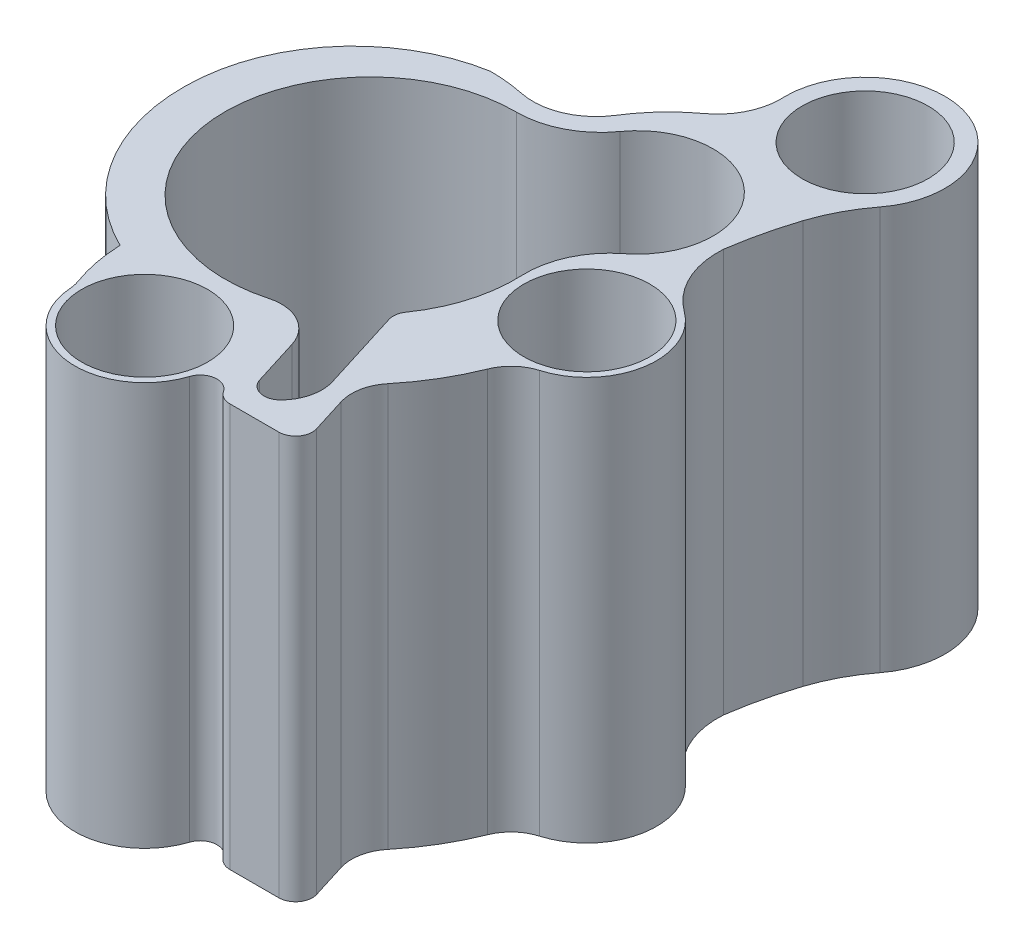
SolidWorks part; units mm, degrees
ref_plane "Front Plane" through (0, 0, 0) normal (0, 0, 1) x (1, 0, 0)
ref_plane "Top Plane" through (0, 0, 0) normal (0, 1, 0) x (1, 0, 0)
ref_plane "Right Plane" through (0, 0, 0) normal (1, 0, 0) x (0, 0, -1)
sketch "Sketch1" plane through (0, 0, 0) normal (0, 1, 0) x (1, 0, 0)
  line L0 (0, 17.0554) -> (0, -17.0554) construction
  line L1 (0, 0) -> (16.3625, 0) construction
  line L2 (5.7372, -9.3535) -> (8.3382, -17.6754)
  line L4 (11.8602, -12.8845) -> (13.7545, -18.9454)
  line L5 (13.7545, -18.9454) -> (7.4045, -18.9454)
  line L6 (6.6404, -16.5007) -> (7.4045, -18.9454)
  line L7 (8.3382, -17.6754) -> (12.027, -17.6754)
  line L8 (12.027, -17.6754) -> (8.6233, -6.7853)
  arc A0 (8.6233, -6.7853) -> (5.7372, -9.3535) centre (0, 0) ccw
  arc A1 (-6.188, 12.7228) -> (-6.188, -12.7228) centre (0, 0) ccw
  arc A2 (5.2705, 17.0554) -> (-5.2705, 17.0554) centre (0, 17.0554) ccw
  arc A4 (16.3625, -5.2705) -> (16.3625, 5.2705) centre (16.3625, 0) ccw
  circle A5 centre (0, 17.0554) radius 4.7625
  circle A6 centre (16.3625, 0) radius 4.7625
  arc A7 (5.2705, -17.0554) -> (-5.2705, -17.0554) centre (0, -17.0554) cw
  circle A8 centre (0, -17.0554) radius 4.7625
  arc A9 (5.2705, 17.0554) -> (16.3625, 5.2705) centre (-2.7565, -1.6119) cw
  arc A10 (16.3625, -5.2705) -> (11.8602, -12.8845) centre (-0.7121, -0.3122) cw
  arc A11 (6.6404, -16.5007) -> (5.2705, -17.0554) centre (-0.7121, -0.3122) cw
  arc A12 (-5.2705, -17.0554) -> (-6.188, -12.7228) centre (6.5049, -12.2983) cw
  arc A13 (-5.2705, 17.0554) -> (-6.188, 12.7228) centre (6.5049, 12.2983) ccw
  point P1 (0, 0)
  point P28 (17.145, 0)
  point P30 (15.7579, 0)
  point P31 (14.8475, 0)
  point P32 (0, 17.0554)
  point P33 (0, 0)
  dimension "D1" = 21.9456
  dimension "D2" = 3.175
  dimension "D4" = 9.525
  dimension "D3" = 9.525
  dimension "D5" = 0.508
  dimension "D6" = 0.508
  dimension "D7" = 20.32
  dimension "D8" = 17.78
  dimension "D13" = 12.7
  dimension "D14" = 6.188
  dimension "D9" = 6.35
  dimension "D10" = 6.35
  dimension "D11" = 6.35
  dimension "D12" = 6.0609
  dimension "D15" = 1.27
  dimension "D16" = 1.27
  dimension "D17" = 1.27
extrude "Boss-Extrude2" add sketch "Sketch1" along normal blind 30.48
fillet "Fillet1" radius 3.175 9 edges at (5.7372, 15.24, 9.3535) (11.8602, 15.24, 12.8845) (5.2705, 15.24, -17.0554) (-5.2705, 15.24, -17.0554) (-5.2705, 15.24, 17.0554) (5.2705, 15.24, 17.0554) (16.3625, 15.24, 5.2705) (16.3625, 15.24, -5.2705) (-6.188, 15.24, -12.7228)
fillet "Fillet3" radius 1.27 2 edges at (13.7545, 15.24, 18.9454) (7.4045, 15.24, 18.9454)
fillet "Fillet4" radius 3.175 1 edges at (12.027, 15.24, 17.6754)
fillet "Fillet5" radius 1.27 1 edges at (8.3382, 15.24, 17.6754)
fillet "Fillet6" radius 1.27 2 edges at (6.6404, 15.24, 16.5007) (8.6233, 15.24, 6.7853)
sketch "Sketch2" plane through (0, 30.48, 0) normal (0, 1, 0) x (1, 0, 0)
  circle A5 centre (9.8968, 10.2919) radius 5.715
  circle A6 centre (9.8968, 10.2919) radius 6.985
  circle A8 centre (0, 0) radius 10.9728
  arc M14 (17.7713, 5.0787) -> (15.7312, 6.8206) centre (18.6199, 8.1382) cw
  arc M15 (15.7312, 6.8206) -> (6.6953, 16.376) centre (-2.7565, -1.6119) ccw
  arc M16 (6.6953, 16.376) -> (5.0999, 18.3854) centre (8.1722, 19.1866) cw
  arc M24 (2.9092, -10.5801) -> (8.9879, -6.2944) centre (0, 0) cw
  dimension "D1" = 11.43
  dimension "D2" = 1.27
extrude "Boss-Extrude9" add sketch "Sketch2" against normal up to surface (30.48 mm away) contours A6 A5 M14 M16 M15 region at (13.2604, 30.48, -15.0944) up to face at (16.3625, 0, 4.7625)
extrude "Cut-Extrude6" cut sketch "Sketch2<12>" against normal blind 30.48 contours A5 M24 M15 region at (9.5924, 30.48, -10.0648)
sketch "Sketch2<12>" plane through (0, 30.48, 0) normal (0, 1, 0) x (1, 0, 0) same geometry as "Sketch2"
fillet "Fillet9" radius 6.35 4 edges at (6.5804, 15.24, -16.4395) (15.8349, 15.24, -6.6137) (9.9724, 15.24, -4.5774) (4.1837, 15.24, -10.1439)
sketch "Sketch3" plane through (0, 30.48, 0) normal (0, 1, 0) x (1, 0, 0)
  line L0 (-7.5055, 11.9928) -> (-2.2961, 12.883)
  line L1 (4.7625, 17.0554) -> (9.7342, 17.2751)
  arc A0 (-7.5055, 11.9928) -> (9.7342, 17.2751) centre (1.4545, 13.5239) cw
  circle A1 centre (0, 17.0554) radius 4.7625 construction
  arc A2 (-2.2961, 12.883) -> (4.7625, 17.0554) centre (0, 17.0554) ccw
extrude "Cut-Extrude7" cut sketch "Sketch3" against normal through all both and the other way through all
sketch "Sketch4" plane through (0, 30.48, 0) normal (0, 1, 0) x (1, 0, 0)
  arc A0 (19.1055, 17.5548) -> (9.2013, 21.7865) centre (15.2215, 22.1706) ccw
  circle A1 centre (15.2215, 22.1706) radius 4.7625
  arc A4 (16.8659, 9.822) -> (9.7342, 17.2751) centre (9.8968, 10.2919) ccw construction
  arc A5 (4.7625, 17.0554) -> (9.189, 22.1706) centre (4.4182, 21.8263) ccw
  arc A6 (19.1055, 17.5548) -> (16.8659, 9.822) centre (45.2516, 5.7916) ccw
  arc M14 (16.8659, 9.822) -> (9.7342, 17.2751) centre (9.8968, 10.2919) ccw
  line M15 (9.7342, 17.2751) -> (4.7625, 17.0554)
  dimension "D1" = 1.27
  dimension "D2" = 9.525
extrude "Boss-Extrude11" add sketch "Sketch4" against normal up to surface (30.48 mm away) contours A6 A0 A5 A1 M15 M14 region at (17.4758, 30.48, -13.8361) up to face at (7.0011, 0, 6.0805)
fillet "Fillet10" radius 12.7 3 edges at (19.1055, 15.24, -17.5548) (-7.5055, 15.24, -11.9928) (4.7625, 15.24, -17.0554)
fillet "Fillet11" radius 12.7 1 edges at (-2.2961, 15.24, -12.883)
sketch "Sketch5" plane through (0, 30.48, 0) normal (0, 1, 0) x (1, 0, 0)
  line B0 (8.816, -7.4018) -> (10.7572, -13.6127)
  line B1 (6.7814, -12.6943) -> (7.8936, -16.253)
  line B2 (8.3382, -18.9454) -> (12.027, -18.9454)
  line B3 (13.2392, -17.2965) -> (12.4021, -14.6183)
  circle B4 centre (15.2215, 22.1706) radius 4.7625
  circle B5 centre (16.3625, 0) radius 4.7625
  circle B6 centre (0, -17.0554) radius 4.7625
  arc B7 (0.0582, 10.9726) -> (2.9092, -10.5801) centre (0, 0) ccw
  arc B8 (13.4063, 5.7814) -> (5.2524, 13.6222) centre (9.8968, 10.2919) ccw
  arc B9 (0.0582, 10.9726) -> (5.2524, 13.6222) centre (0.0919, 17.3226) ccw
  arc B10 (10.962, 0.4876) -> (13.4063, 5.7814) centre (17.3057, 0.7698) cw
  arc B11 (8.9879, -6.2944) -> (8.816, -7.4018) centre (10.0282, -7.023) ccw
  arc B12 (6.7814, -12.6943) -> (2.9092, -10.5801) centre (3.7509, -13.6415) ccw
  arc B13 (10.7572, -13.6127) -> (10.0251, -16.7503) centre (7.7268, -14.5598) cw
  arc B14 (10.0251, -16.7503) -> (7.8936, -16.253) centre (9.1058, -15.8741) cw
  arc B15 (8.9879, -6.2944) -> (10.962, 0.4876) centre (0, 0) ccw
  arc B16 (20.0035, 18.4931) -> (9.189, 22.1706) centre (15.2215, 22.1706) ccw
  arc B17 (9.189, 22.1706) -> (7.2496, 17.9711) centre (4.4182, 21.8263) cw
  arc B18 (7.2496, 17.9711) -> (4.0274, 14.5135) centre (14.7672, 7.7351) ccw
  arc B19 (4.0274, 14.5135) -> (-0.9762, 12.3941) centre (0, 17.0554) cw
  arc B20 (-3.5797, 12.6637) -> (-0.9762, 12.3941) centre (-3.5792, -0.0363) cw
  arc B21 (-3.5797, 12.6637) -> (-14.0765, 1.4183) centre (-1.4405, 0.1451) ccw
  arc B22 (-14.0765, 1.4183) -> (-6.188, -12.7228) centre (0, 0) ccw
  arc B23 (-6.188, -12.7228) -> (-5.4353, -16.6252) centre (6.5049, -12.2983) ccw
  arc B24 (-5.4353, -16.6252) -> (-5.2548, -17.462) centre (-8.4203, -17.707) cw
  arc B25 (-5.2548, -17.462) -> (5.0123, -18.6847) centre (0, -17.0554) ccw
  arc B26 (5.0123, -18.6847) -> (7.2792, -18.3764) centre (6.2201, -19.0773) cw
  arc B27 (7.2792, -18.3764) -> (8.3382, -18.9454) centre (8.3382, -17.6754) ccw
  arc B28 (12.027, -18.9454) -> (13.2392, -17.2965) centre (12.027, -17.6754) ccw
  arc B29 (12.4021, -14.6183) -> (12.9864, -11.6471) centre (15.4325, -13.6711) cw
  arc B30 (12.9864, -11.6471) -> (15.7931, -6.9233) centre (-0.7121, -0.3122) ccw
  arc B31 (15.7931, -6.9233) -> (17.8465, -5.0573) centre (18.7404, -8.1038) cw
  arc B32 (17.8465, -5.0573) -> (19.4644, 4.2611) centre (16.3625, 0) ccw
  arc B33 (19.4644, 4.2611) -> (16.8659, 9.822) centre (23.2016, 9.3949) cw
  arc B34 (20.0035, 18.4931) -> (17.9987, 14.695) centre (30.0708, 10.7511) ccw
  arc B35 (17.9987, 14.695) -> (16.8659, 9.822) centre (45.2516, 5.7916) ccw
sketch_block_instance "Block1-1"
sketch_block "Block1"
